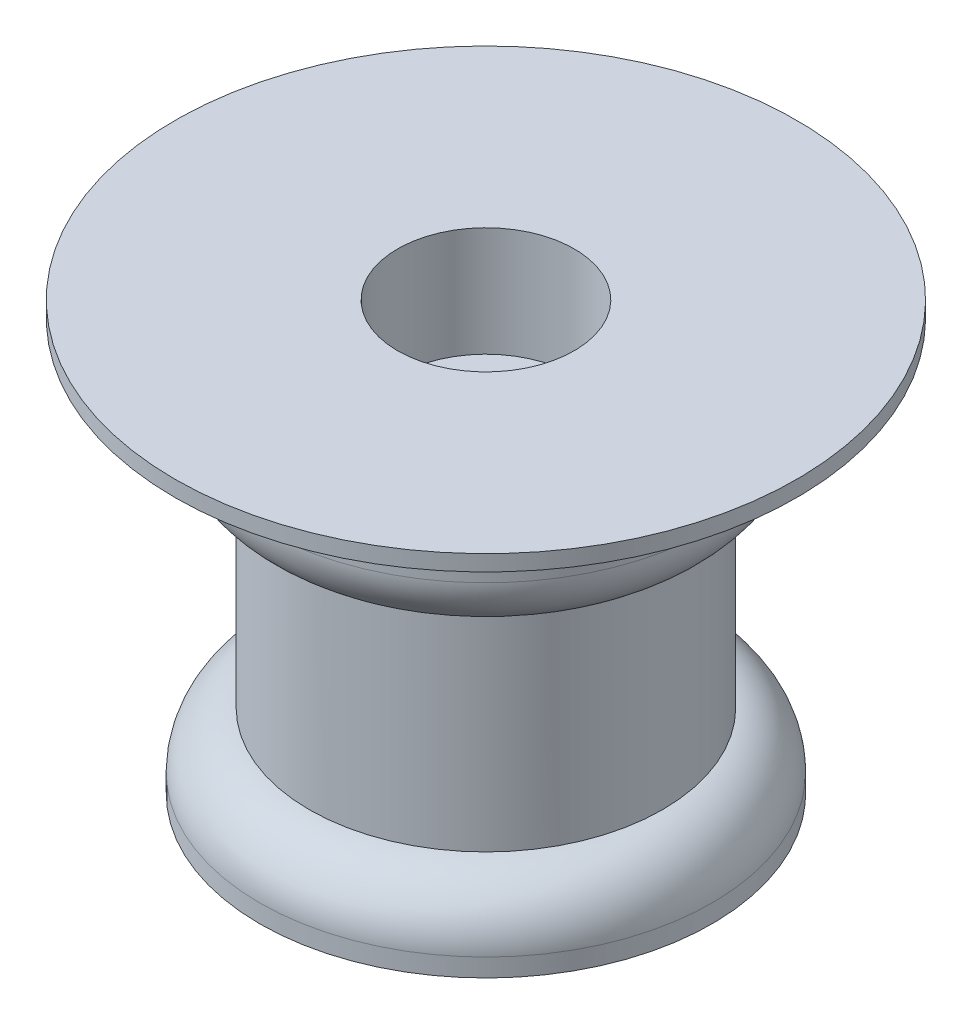
SolidWorks part; units mm, degrees
ref_plane "Спереди" through (0, 0, 0) normal (0, 0, 1) x (1, 0, 0)
ref_plane "Сверху" through (0, 0, 0) normal (0, 1, 0) x (1, 0, 0)
ref_plane "Справа" through (0, 0, 0) normal (1, 0, 0) x (0, 0, -1)
sketch "Эскиз1" plane through (0, 0, 0) normal (0, 1, 0) x (1, 0, 0)
  circle A0 centre (0, 0) radius 2.3
  circle A1 centre (0, 0) radius 32
  dimension "D1" = 4.6
  dimension "D2" = 64
extrude "Бобышка-Вытянуть1" add sketch "Эскиз1" along normal blind 51
sketch "Эскиз2" plane through (0, 0, 0) normal (0, -1, 0) x (1, 0, 0)
  circle A0 centre (0, 0) radius 13.15
  point P0 (0, 0)
  dimension "D1" = 26.3
extrude "Вырез-Вытянуть1" cut sketch "Эскиз2" against normal blind 40
sketch "Эскиз16" plane through (0, 0, 0) normal (0, -1, 0) x (1, 0, 0)
  circle A0 centre (0, 0) radius 25
  circle A1 centre (0, 0) radius 36.6999
  dimension "D1" = 50
extrude "Вырез-Вытянуть5" cut sketch "Эскиз16" against normal blind 30 from offset 10.5 offset against normal yes
fillet "Скругление4" radius 8 2 edges at (0, 10.5, -32) (0, 40.5, -32)
sketch "Эскиз17" plane through (0, 51, 0) normal (0, 1, 0) x (1, 0, 0)
  circle A0 centre (0, 0) radius 12.5
  dimension "D1" = 25
extrude "Вырез-Вытянуть6" cut sketch "Эскиз17" against normal blind 6
sketch "Эскиз18" plane through (0, 51, 0) normal (0, 1, 0) x (1, 0, 0)
  circle A0 centre (0, 0) radius 12.5
  circle A1 centre (0, 0) radius 32
extrude "Бобышка-Вытянуть2" add sketch "Эскиз18" along normal blind 7.25
sketch "Эскиз19" plane through (0, 58.25, 0) normal (0, 1, 0) x (1, 0, 0)
  circle A0 centre (0, 0) radius 12.5
  circle A1 centre (0, 0) radius 44
  circle A2 centre (0, 0) radius 12.5 construction
  dimension "D1" = 88
extrude "Бобышка-Вытянуть3" add sketch "Эскиз19" along normal blind 2.25
fillet "Скругление5" radius 8 1 edges at (0, 58.25, 32)
